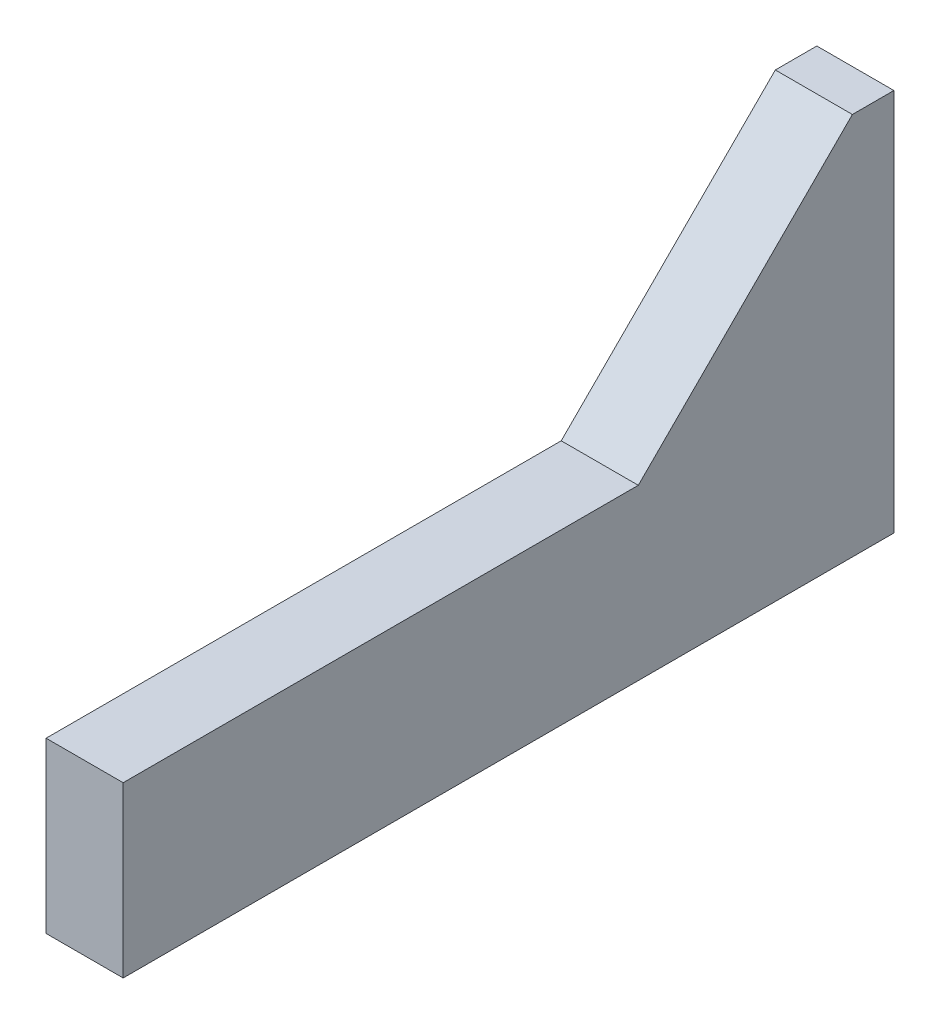
SolidWorks part; units mm, degrees
ref_plane "Спереди" through (0, 0, 0) normal (0, 0, 1) x (1, 0, 0)
ref_plane "Сверху" through (0, 0, 0) normal (0, 1, 0) x (1, 0, 0)
ref_plane "Справа" through (0, 0, 0) normal (1, 0, 0) x (0, 0, -1)
sketch "Эскиз1" plane through (0, 0, 0) normal (0, 0, 1) x (1, 0, 0)
  line L1 (-4.5, -7.5) -> (4.5, -7.5)
  line L2 (-4.5, -7.5) -> (-4.5, 7.5)
  line L3 (-4.5, 7.5) -> (4.5, 7.5)
  line L4 (4.5, -7.5) -> (4.5, 7.5)
  line L5 (-4.5, -7.5) -> (4.5, 7.5) construction
  line L6 (-4.5, 7.5) -> (4.5, -7.5) construction
  line L7 (-4.5, 7.5) -> (4.5, 7.5)
  line L8 (-4.5, 7.5) -> (-4.5, 12.25)
  line L9 (-4.5, 12.25) -> (4.5, 12.25)
  line L10 (4.5, 7.5) -> (4.5, 12.25)
  line L11 (4.5, 7.5) -> (-0.5, 7.5)
  line L12 (4.5, 7.5) -> (4.5, 9.75)
  line L13 (4.5, 9.75) -> (-0.5, 9.75)
  line L14 (-0.5, 7.5) -> (-0.5, 9.75)
  point P0 (0, 0)
  dimension "D1" = 9
  dimension "D2" = 15
  dimension "D3" = 2.25
  dimension "D4" = 2.5
  dimension "D5" = 4
extrude "Бобышка-Вытянуть1" add sketch "Эскиз1" along normal blind 90 contours L1 L4 L7 L3 L2 | L3 L14 L13 L10 L9 L8 region at (0, 0, 0) region at (-0.7143, 10.3214, 0)
sketch "Эскиз2" plane through (0, -7.5, 0) normal (0, -1, 0) x (1, 0, 0)
  line L0 (0, 90) -> (0, 67.5) construction
  line L1 (-4.5, 90) -> (4.5, 90) construction
  line L2 (0, 67.5) -> (0, 45) construction
  line L3 (0, 22.5) -> (0, 0) construction
  line L4 (-4.5, 0) -> (4.5, 0) construction
  line L5 (0, 45) -> (0, 22.5) construction
  circle A0 centre (0, 22.5) radius 2.1
  circle A1 centre (0, 67.5) radius 2.1
  circle A2 centre (0, 45) radius 2.1
  dimension "D1" = 4.2
extrude "Вырез-Вытянуть1" cut sketch "Эскиз2" against normal blind 6
sketch "Эскиз3" plane through (0, 0, 90) normal (0, 0, -1) x (-1, 0, 0)
  line L1 (-4.5, 9.75) -> (0.5, 9.75)
  line L2 (-4.5, 9.75) -> (-4.5, 7.5)
  line L3 (-4.5, 7.5) -> (0.5, 7.5)
  line L4 (0.5, 9.75) -> (0.5, 7.5)
extrude "Бобышка-Вытянуть2" add sketch "Эскиз3" along normal blind 3
chamfer "Фаска1" distance 0.75 angle 45 2 edges at (4.5, 7.5, 43.5) (4.5, 9.75, 43.5)
sketch "Эскиз5" plane through (-4.5, 0, 0) normal (-1, 0, 0) x (0, 0, 1)
  line L0 (0, 12.25) -> (0, 37.25)
  line L1 (0, 37.25) -> (4.8479, 37.25)
  line L2 (4.8479, 37.25) -> (29.8479, 12.25)
  line L3 (90, 12.25) -> (0, 12.25) construction
  line L4 (0, 12.25) -> (29.8479, 12.25)
  dimension "D1" = 45
  dimension "D2" = 25
extrude "Бобышка-Вытянуть3" add sketch "Эскиз5" against normal up to surface (9 mm away) contours L1 L2 L4 L0 up to face at (4.5, 5.5, 44.25)
sketch "Эскиз4" plane through (0, 0, 0) normal (0, 0, -1) x (-1, 0, 0)
  line L0 (-4.5, 37.25) -> (4.5, 37.25) construction
  line L1 (4.5, -7.5) -> (-4.5, -7.5) construction
  circle A0 centre (0, 2.5) radius 2.1
  circle A1 centre (0, 27.25) radius 2.1
  dimension "D1" = 4.2
  dimension "D2" = 10
  dimension "D3" = 10
extrude "Вырез-Вытянуть2" cut sketch "Эскиз4" against normal blind 6
mirror "Зеркальное отражение1" about plane through (-4.5, 0, 90) normal (-1, 0, 0) of bodies 104
delete or keep bodies "Тело-Удалить/Сохранить 1" type delete bodies bodies 104
